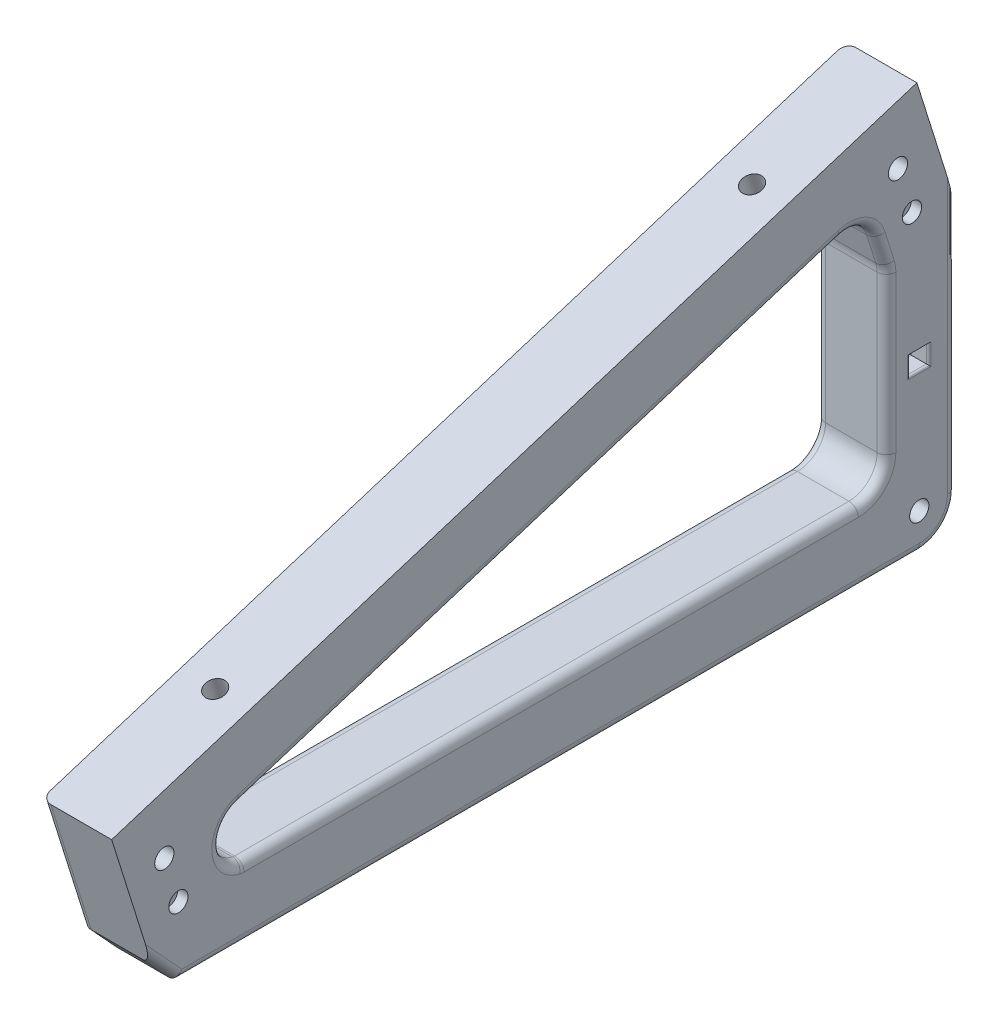
SolidWorks part; units mm, degrees
ref_plane "Front Plane" through (0, 0, 0) normal (0, 0, 1) x (1, 0, 0)
ref_plane "Top Plane" through (0, 0, 0) normal (0, 1, 0) x (1, 0, 0)
ref_plane "Right Plane" through (0, 0, 0) normal (1, 0, 0) x (0, 0, -1)
sketch "Sketch2" plane through (0, 0, 0) normal (1, 0, 0) x (0, 0, -1)
  line L2 (190.7135, 8) -> (190.7135, 60.2286)
  line L3 (182.2032, 87.3274) -> (10.4725, 33.3965)
  line L4 (165.9731, 66.5082) -> (37.6594, 26.2121)
  line L6 (38.484, 15.2818) -> (169.7135, 15.2818)
  line L8 (175.7135, 15) -> (175.7135, 69.5671) construction
  line L9 (175.7135, 69.5671) -> (25.4725, 22.3849) construction
  line L10 (25.4725, 15) -> (175.7135, 15) construction
  line L11 (25.4725, 15) -> (25.4725, 22.3849) construction
  line L13 (175.7135, 54.5979) -> (175.7135, 21.2818)
  line L14 (175.7135, 65.5568) -> (175.7135, 70.3181)
  line L16 (182.2032, 87.3274) -> (190.7135, 60.2286)
  line L17 (190.7135, 90) -> (138.5647, 90) construction
  line L18 (190.7135, 8) -> (190.7135, 90) construction
  line L19 (190.7135, 90) -> (10.4725, 33.3965) construction
  line L20 (190.7135, 60.2286) -> (154.4697, 48.8465) construction
  line L21 (175.4378, 56.3956) -> (173.4952, 62.5815)
  line L22 (10.4725, 33.3965) -> (19.0969, 5.9339)
  line L24 (8, 0) -> (182.7135, 0) construction
  line L25 (10.4725, 6.3965) -> (10.4725, 33.3965) construction
  line L26 (14.975, 0) -> (-18.4794, 0) construction
  line L27 (24.5513, 0) -> (14.975, 0) construction
  line L28 (10.4725, 33.3965) -> (-10.5052, 26.8086) construction
  line L29 (19.0969, 5.9339) -> (24.5513, 0)
  line L30 (24.5513, 0) -> (182.7135, 0)
  arc A1 (182.7135, 0) -> (190.7135, 8) centre (182.7135, 8) ccw
  arc A6 (175.7135, 15) -> (175.7135, 15) centre (175.7135, 15) ccw construction
  arc A7 (25.4725, 15) -> (25.4725, 15) centre (25.4725, 15) cw construction
  arc A9 (175.7135, 21.2818) -> (169.7135, 15.2818) centre (169.7135, 21.2818) cw
  arc A14 (173.4952, 62.5815) -> (165.9731, 66.5082) centre (167.7708, 60.7838) ccw
  arc A15 (175.7135, 54.5979) -> (175.4378, 56.3956) centre (169.7135, 54.5979) ccw
  arc A18 (8, 0) -> (10.4725, 6.3965) centre (15.978, 0.5923) cw construction
  arc A20 (37.9384, 26.2997) -> (38.484, 15.2818) centre (39.4952, 20.8543) ccw
  point P7 (0, 0)
  point P10 (190.7135, 0)
  point P40 (175.7135, 55.5179)
  dimension "D4" = 180
  dimension "D5" = 8
  dimension "D7" = 15
  dimension "D8" = 6
  dimension "D10" = 6
  dimension "D13" = 6
  dimension "D2" = 90
  dimension "D3" = 35
  dimension "D12" = 8.92
  dimension "D6" = 15
extrude "Boss-Extrude1" add sketch "Sketch2" along normal blind 15 contours A1 L2 L3 L4 L13 A9 L6 region at (0, 3.7594, -186.9541)
sketch "Sketch3" plane through (0, 27.4049, 8.6063) normal (0, 0.9541, 0.2996) x (1, 0, 0)
  line L0 (7.5, 199.9975) -> (7.5, 19.9975) construction
  line L1 (15, 199.9975) -> (0, 199.9975) construction
  line L2 (15, 19.9975) -> (0, 19.9975) construction
  line L3 (0, 199.9975) -> (0, 19.9975) construction
  circle A0 centre (7.5, 170.9975) radius 2.1
  circle A1 centre (7.5, 50.9975) radius 2.1
  dimension "D2" = 4.2
  dimension "D3" = 4.2
  dimension "D1" = 7.5
  dimension "D4" = 120
  dimension "D5" = 29
extrude "Cut-Extrude1" cut sketch "Sketch3" against normal up to next
sketch "Sketch4" plane through (0, 13.094, 4.1121) normal (0, -0.9541, -0.2996) x (1, 0, 0)
  line L0 (3.9103, -172.9768) -> (7.4193, -175.0959)
  line L1 (7.3023, -46.9031) -> (3.8553, -49.1215)
  line L2 (3.8553, -49.1215) -> (4.053, -53.2159)
  line L3 (4.053, -53.2159) -> (7.6977, -55.0919)
  line L4 (7.6977, -55.0919) -> (11.1447, -52.8735)
  line L5 (11.1447, -52.8735) -> (10.947, -48.7791)
  line L6 (10.947, -48.7791) -> (7.3023, -46.9031)
  line L7 (7.4193, -175.0959) -> (11.009, -173.1166)
  line L8 (11.009, -173.1166) -> (11.0897, -169.0182)
  line L9 (11.0897, -169.0182) -> (7.5807, -166.8991)
  line L10 (7.5807, -166.8991) -> (3.991, -168.8784)
  line L11 (3.991, -168.8784) -> (3.9103, -172.9768)
  line L12 (11.009, -173.1166) -> (3.991, -168.8784) construction
  circle A0 centre (7.5, -50.9975) radius 3.55 construction
  point P15 (7.5, -170.9975)
  point P16 (11.0459, -50.8263)
  dimension "D1" = 7.1
extrude "Cut-Extrude2" cut sketch "Sketch4" against normal blind 8
sketch "Sketch5" plane through (0, 0, 0) normal (-1, 0, 0) x (0, 0, 1)
  line L1 (-182.2032, 87.3274) -> (-190.7135, 60.2286) construction
  line L2 (-10.4725, 33.3965) -> (-19.0969, 5.9339) construction
  line L3 (-182.2032, 87.3274) -> (-10.4725, 33.3965) construction
  circle A0 centre (-178.1662, 73.4818) radius 2.05
  circle A1 centre (-178.1662, 73.4818) radius 4
  circle A2 centre (-182.7135, 8) radius 2.05
  circle A3 centre (-182.7135, 8) radius 4
  circle A4 centre (-21.7004, 24.3447) radius 2.05
  circle A5 centre (-21.7004, 24.3447) radius 4
  dimension "D3" = 4.1
  dimension "D4" = 4.1
  dimension "D5" = 8
  dimension "D8" = 4.1
  dimension "D1" = 8
  dimension "D2" = 12
  dimension "D6" = 12
  dimension "D7" = 8
extrude "Cut-Extrude3" cut sketch "Sketch5" against normal through all contours A0 | A2 | A4
extrude "Cut-Extrude4" cut sketch "Sketch5<3>" against normal blind 3 contours A2 | A3 | A1 | A5
sketch "Sketch5<3>" plane through (0, 0, 0) normal (-1, 0, 0) x (0, 0, 1) same geometry as "Sketch5"
sketch "Sketch6" plane through (15, 0, 0) normal (1, 0, 0) x (0, 0, -1)
  line L0 (182.2032, 87.3274) -> (190.7135, 60.2286) construction
  line L1 (10.4725, 33.3965) -> (19.0969, 5.9339) construction
  line L2 (182.2032, 87.3274) -> (10.4725, 33.3965) construction
  circle A0 centre (24.6965, 14.8041) radius 2.05
  circle A1 centre (181.1623, 63.9412) radius 2.05
  dimension "D1" = 4.1
  dimension "D2" = 4.1
  dimension "D3" = 8
  dimension "D4" = 8
  dimension "D5" = 22
  dimension "D6" = 22
extrude "Cut-Extrude5" cut sketch "Sketch6" against normal blind 2.2
fillet "Fillet1" radius 2 27 edges at (15, 46.4039, -101.9557) (15, 66.1027, -170.5474) (15, 59.4886, -174.4665) (15, 55.5073, -175.6442) (15, 37.9399, -175.7135) (15, 17.0391, -173.9561) (0, 46.4039, -101.9557) (0, 66.1027, -170.5474) (0, 59.4886, -174.4665) (0, 55.5073, -175.6442) (0, 37.9399, -175.7135) (0, 17.0391, -173.9561) (0, 2.3431, -188.3703) (15, 15.2818, -104.0987) (0, 15.2818, -104.0987) (0, 19.6652, -14.7847) (0, 34.1143, -190.7135) (0, 73.778, -186.4584) (15, 34.1143, -190.7135) (15, 2.3431, -188.3703) (15, 20.5742, -33.8386) (0, 20.5742, -33.8386) (0, 0, -103.6324) (7.5, 15.2818, -38.484) (15, 2.967, -21.8241) (15, 0, -103.6324) (0, 2.967, -21.8241)
sketch "Sketch7" plane through (15, 0, 0) normal (1, 0, 0) x (0, 0, -1)
  line L0 (182.7135, 8) -> (182.7135, 38) construction
  line L1 (180.7135, 38) -> (184.7135, 38)
  line L3 (184.7135, 38) -> (180.7135, 38)
  line L4 (184.7135, 38) -> (184.7135, 33.9)
  line L5 (184.7135, 33.9) -> (180.7135, 33.9)
  line L6 (180.7135, 38) -> (180.7135, 33.9)
  point P6 (182.7135, 38)
  dimension "D1" = 30
  dimension "D2" = 4
  dimension "D3" = 4.1
extrude "Cut-Extrude6" cut sketch "Sketch7" against normal blind 4.2 contours L5 L0 L1 L6 | L0 L5 L4 L3 region at (15, 35.95, -181.7135) region at (15, 35.95, -183.7135)
fillet "Fillet2" radius 0.5 7 edges at (10.8, 35.95, -184.7135) (10.8, 38, -182.7135) (10.8, 35.95, -180.7135) (10.8, 33.9, -182.7135) (15, 35.95, -180.7135) (15, 33.9, -182.7135) (15, 35.95, -184.7135) tangent propagation no
